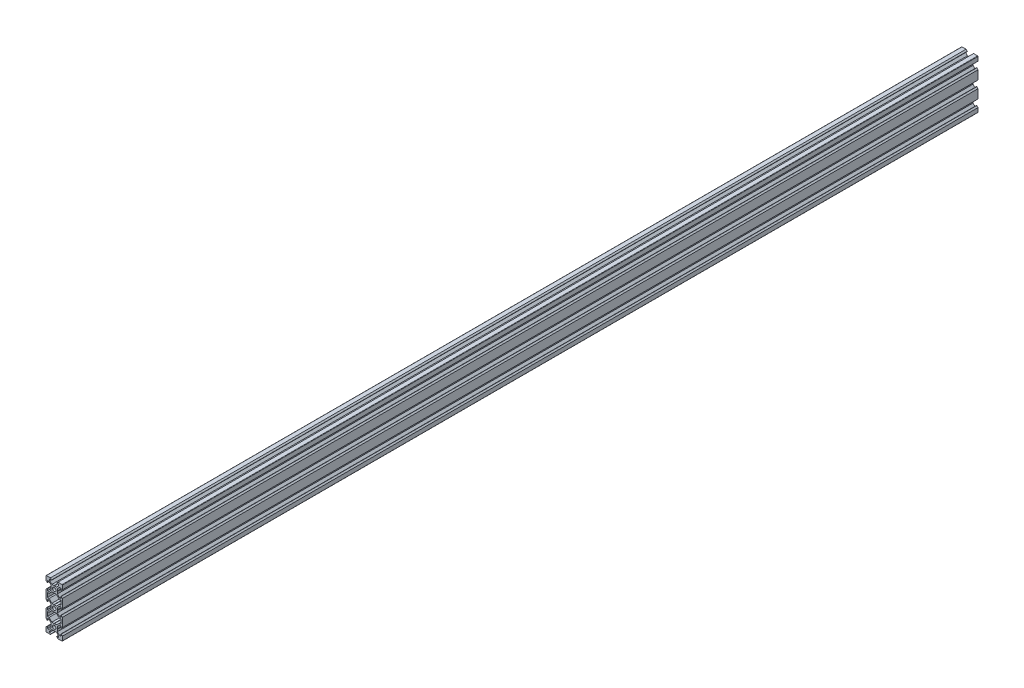
SolidWorks part; units mm, degrees
ref_plane "Plan de face" through (0, 0, 0) normal (0, 0, 1) x (1, 0, 0)
ref_plane "Plan de dessus" through (0, 0, 0) normal (0, 1, 0) x (1, 0, 0)
ref_plane "Plan de droite" through (0, 0, 0) normal (1, 0, 0) x (0, 0, -1)
ref_axis "Axe" through (0, 0, -13.782) along (0, 0, 1)
sketch "Esquisse1" plane through (0, 0, 0) normal (0, 0, 1) x (1, 0, 0)
  line L0 (0, 27.6392) -> (0, -27.6392) construction
  line L1 (-33.6074, 0) -> (33.6074, 0) construction
  line L2 (0, 0) -> (-22.2114, 22.2114) construction
  line L3 (-9.5, 10) -> (-4.58, 10)
  line L4 (-4.58, 10) -> (-3.125, 8.545)
  line L5 (-3.125, 8.545) -> (-3.125, 8.2)
  line L6 (-3.125, 8.2) -> (-5.5, 8.2)
  line L7 (-2.8393, 3.9) -> (-5.5, 6.5607)
  line L8 (-2.8393, 3.9) -> (-0.21, 3.9)
  line L9 (-5.5, 6.5607) -> (-5.5, 8.2)
  line L10 (0, 3.69) -> (0, 2.1)
  line L11 (-3.9, 2.8393) -> (-6.5607, 5.5)
  line L12 (-8.545, 3.125) -> (-8.2, 3.125)
  line L13 (-8.2, 3.125) -> (-8.2, 5.5)
  line L14 (-6.5607, 5.5) -> (-8.2, 5.5)
  line L15 (-10, 4.58) -> (-8.545, 3.125)
  line L16 (-10, 9.5) -> (-10, 4.58)
  line L17 (-0.21, 3.9) -> (0, 3.69)
  line L18 (-3.9, 2.8393) -> (-3.9, 0.21)
  line L19 (-6.2393, -12.7) -> (-8.2, -12.7)
  line L20 (-3.9, 0.21) -> (-3.69, 0)
  line L21 (-0.21, -3.9) -> (0, -3.69)
  line L22 (0, -3.69) -> (0, -2.1)
  line L23 (-6.5607, -5.5) -> (-8.2, -5.5)
  line L24 (-2.8393, -3.9) -> (-0.21, -3.9)
  line L25 (-8.545, -3.125) -> (-8.2, -3.125)
  line L26 (-10, -4.58) -> (-8.545, -3.125)
  line L27 (-8.2, -3.125) -> (-8.2, -5.5)
  line L28 (-2.8393, -3.9) -> (-6.2393, -7.3)
  line L29 (-3.9, -2.8393) -> (-6.5607, -5.5)
  line L30 (-3.9, -2.8393) -> (-3.9, -0.21)
  line L31 (-3.9, -0.21) -> (-3.69, 0)
  line L32 (-6.2393, -7.3) -> (-8.2, -7.3)
  line L33 (-8.2, -7.3) -> (-8.2, -12.7)
  line L34 (-8.2, -10) -> (-10, -10) construction
  line L35 (-10, -15.42) -> (-10, -4.58)
  line L36 (-3.9, -19.79) -> (-3.69, -20)
  line L37 (-3.9, -17.1607) -> (-3.9, -19.79)
  line L38 (-3.9, -17.1607) -> (-6.5607, -14.5)
  line L39 (-2.8393, -16.1) -> (-6.2393, -12.7)
  line L40 (-8.2, -16.875) -> (-8.2, -14.5)
  line L41 (-10, -15.42) -> (-8.545, -16.875)
  line L42 (-8.545, -16.875) -> (-8.2, -16.875)
  line L43 (-2.8393, -16.1) -> (-0.21, -16.1)
  line L44 (-6.5607, -14.5) -> (-8.2, -14.5)
  line L45 (0, -16.31) -> (0, -17.9)
  line L46 (-0.21, -16.1) -> (0, -16.31)
  line L47 (-8.2, -30) -> (-10, -30) construction
  line L48 (-3.69, -20) -> (0, -20) construction
  line L49 (-0.21, -23.9) -> (0, -23.69)
  line L50 (0, -23.69) -> (0, -22.1)
  line L51 (-6.5607, -25.5) -> (-8.2, -25.5)
  line L52 (-2.8393, -23.9) -> (-0.21, -23.9)
  line L53 (-8.545, -23.125) -> (-8.2, -23.125)
  line L54 (-10, -24.58) -> (-8.545, -23.125)
  line L55 (-8.2, -23.125) -> (-8.2, -25.5)
  line L56 (-2.8393, -23.9) -> (-6.2393, -27.3)
  line L57 (-3.9, -22.8393) -> (-6.5607, -25.5)
  line L58 (-3.9, -22.8393) -> (-3.9, -20.21)
  line L59 (-3.9, -20.21) -> (-3.69, -20)
  line L60 (-10, -24.58) -> (-10, -35.42)
  line L61 (-8.2, -32.7) -> (-8.2, -27.3)
  line L62 (-6.2393, -32.7) -> (-8.2, -32.7)
  line L63 (-3.9, -39.79) -> (-3.69, -40)
  line L64 (-3.9, -37.1607) -> (-3.9, -39.79)
  line L65 (-3.9, -37.1607) -> (-6.5607, -34.5)
  line L66 (-2.8393, -36.1) -> (-6.2393, -32.7)
  line L67 (-8.2, -36.875) -> (-8.2, -34.5)
  line L68 (-10, -35.42) -> (-8.545, -36.875)
  line L69 (-8.545, -36.875) -> (-8.2, -36.875)
  line L70 (-2.8393, -36.1) -> (-0.21, -36.1)
  line L71 (-6.5607, -34.5) -> (-8.2, -34.5)
  line L72 (0, -36.31) -> (0, -37.9)
  line L73 (-0.21, -36.1) -> (0, -36.31)
  line L74 (-3.9, -40.21) -> (-3.69, -40)
  line L75 (-6.2393, -27.3) -> (-8.2, -27.3)
  line L76 (-3.9, -42.8393) -> (-3.9, -40.21)
  line L77 (-0.21, -43.9) -> (0, -43.69)
  line L78 (-10, -49.5) -> (-10, -44.58)
  line L79 (-10, -44.58) -> (-8.545, -43.125)
  line L80 (-6.5607, -45.5) -> (-8.2, -45.5)
  line L81 (-8.2, -43.125) -> (-8.2, -45.5)
  line L82 (-8.545, -43.125) -> (-8.2, -43.125)
  line L83 (-3.9, -42.8393) -> (-6.5607, -45.5)
  line L84 (0, -43.69) -> (0, -42.1)
  line L85 (-5.5, -46.5607) -> (-5.5, -48.2)
  line L86 (-2.8393, -43.9) -> (-0.21, -43.9)
  line L87 (-2.8393, -43.9) -> (-5.5, -46.5607)
  line L88 (-3.125, -48.2) -> (-5.5, -48.2)
  line L89 (-3.125, -48.545) -> (-3.125, -48.2)
  line L90 (-4.58, -50) -> (-3.125, -48.545)
  line L91 (-9.5, -50) -> (-4.58, -50)
  arc A0 (0, -2.1) -> (0, 2.1) centre (0, 0) cw
  arc A1 (-9.5, 10) -> (-10, 9.5) centre (-9.5, 9.5) ccw
  arc A2 (0, -37.9) -> (0, -42.1) centre (0, -40) ccw
  arc A3 (-9.5, -50) -> (-10, -49.5) centre (-9.5, -49.5) cw
  arc A4 (0, -17.9) -> (0, -22.1) centre (0, -20) ccw
  point P4 (0, 0)
  point P7 (0, 0)
  point P30 (-10, 10)
  point P60 (0, -20)
  point P111 (-10, -50)
  dimension "D5" = 11
  dimension "D2" = 2.1
  dimension "D3" = 6.25
  dimension "D10" = 0.5
  dimension "D4" = 9.16
  dimension "D6" = 1.5
  dimension "D7" = 1.8
  dimension "D8" = 4.3
  dimension "D9" = 20
  dimension "D11" = 0.42
  dimension "D12" = 10
  dimension "D13" = 1.8
extrude "Boss.-Extru.1" add sketch "Esquisse1" along normal blind 1120
sketch "Esquisse3" plane through (0, 0, 1120) normal (0, 0, 1) x (1, 0, 0)
  line L0 (0, 0) -> (-9.8536, 9.8536) construction
  line L1 (-8.2, 8.2) -> (-8.2, 6.57)
  line L2 (-8.2, 6.57) -> (-7.54, 6.57)
  line L3 (-7.54, 6.57) -> (-6.57, 7.54)
  line L4 (-8.2, 3.125) -> (-8.2, 5.5) construction
  line L5 (-6.57, 8.2) -> (-6.57, 7.54)
  line L6 (-8.2, 8.2) -> (-6.57, 8.2)
  line L7 (-5.5, 6.5607) -> (-5.5, 8.2) construction
  line L8 (-3.69, -20) -> (0, -20) construction
  line L9 (-8.2, -48.2) -> (-6.57, -48.2)
  line L10 (-6.57, -48.2) -> (-6.57, -47.54)
  line L11 (-7.54, -46.57) -> (-6.57, -47.54)
  line L12 (-8.2, -46.57) -> (-7.54, -46.57)
  line L13 (-8.2, -48.2) -> (-8.2, -46.57)
  arc A0 (-9.5, 10) -> (-10, 9.5) centre (-9.5, 9.5) ccw construction
  point P13 (-7.055, 7.055)
  point P14 (-6.57, 7.87)
  point P26 (-7.055, -47.055)
  dimension "D1" = 1.07
extrude "Enlèv. mat.-Extru.1" [suppressed] cut sketch "Esquisse3" against normal through all
mirror "Symétrie1" about plane through (0, 3.69, 1120) normal (-1, 0, 0) of "Enlèv. mat.-Extru.1", "Boss.-Extru.1"
